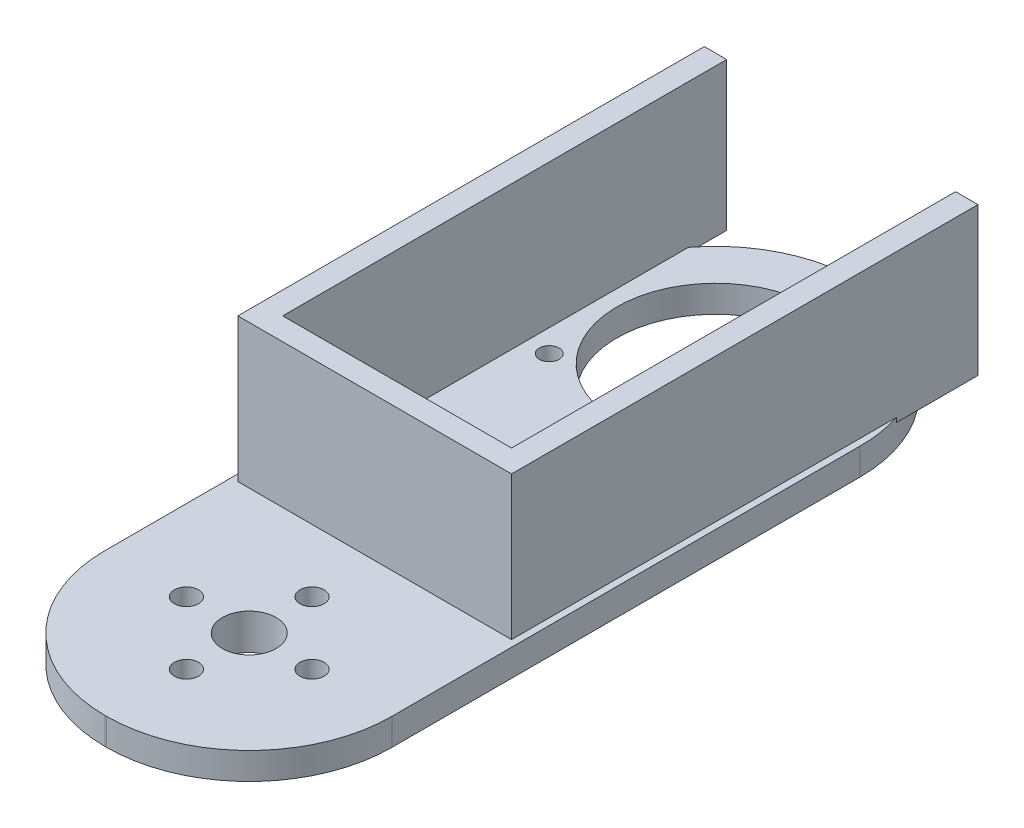
SolidWorks part; units mm, degrees
ref_plane "Front Plane" through (0, 0, 0) normal (0, 0, 1) x (1, 0, 0)
ref_plane "Top Plane" through (0, 0, 0) normal (0, 1, 0) x (1, 0, 0)
ref_plane "Right Plane" through (0, 0, 0) normal (1, 0, 0) x (0, 0, -1)
sketch "S_cyl1" plane through (0, 0, 0) normal (0, 1, 0) x (1, 0, 0)
  circle A0 centre (0, 0) radius 11
  dimension "D1_S_cyl1" = 22
extrude "Boss_1" add sketch "S_cyl1" along normal blind 1.1
ref_plane "PY_p1_000" through (0, 1, 0) normal (0, 1, 0) x (1, 0, 0)
sketch "S_prism2" plane through (0, 1, 0) normal (0, 1, 0) x (1, 0, 0)
  line L0 (-0.1, -16) -> (0.1, -16)
  line L1 (16, -0.1) -> (16, 52.1)
  line L2 (0.1, 68) -> (-0.1, 68)
  line L3 (-16, 52.1) -> (-16, -0.1)
  arc A0 (-16, -0.1) -> (-0.1, -16) centre (-0.1, -0.1) ccw
  arc A1 (0.1, -16) -> (16, -0.1) centre (0.1, -0.1) ccw
  arc A2 (16, 52.1) -> (0.1, 68) centre (0.1, 52.1) ccw
  arc A3 (-0.1, 68) -> (-16, 52.1) centre (-0.1, 52.1) ccw
extrude "Boss_2" add sketch "S_prism2" along normal blind 3
ref_plane "PZ_m66_000" through (0, 0, -66) normal (0, 0, 1) x (1, 0, 0)
sketch "S_box3" plane through (0, 0, -66) normal (0, 0, 1) x (1, 0, 0)
  line L0 (12.76, 3.5) -> (15.26, 3.5)
  line L1 (15.26, 3.5) -> (15.26, 20)
  line L2 (15.26, 20) -> (12.76, 20)
  line L3 (12.76, 20) -> (12.76, 3.5)
  dimension "P1" = 12.76
  dimension "P2" = 3.5
  dimension "P3" = 15.26
  dimension "P4" = 3.5
  dimension "P5" = 15.26
  dimension "P6" = 20
  dimension "P7" = 12.76
  dimension "P8" = 20
extrude "Boss_3" add sketch "S_box3" along normal blind 52.01
sketch "S_box4" plane through (0, 0, -66) normal (0, 0, 1) x (1, 0, 0)
  line L0 (-15.26, 3.5) -> (-12.76, 3.5)
  line L1 (-12.76, 3.5) -> (-12.76, 20)
  line L2 (-12.76, 20) -> (-15.26, 20)
  line L3 (-15.26, 20) -> (-15.26, 3.5)
  dimension "P1" = 15.26
  dimension "P2" = 3.5
  dimension "P3" = 12.76
  dimension "P4" = 3.5
  dimension "P5" = 12.76
  dimension "P6" = 20
  dimension "P7" = 15.26
  dimension "P8" = 20
extrude "Boss_4" add sketch "S_box4" along normal blind 52.01
ref_plane "PZ_m16_490" through (0, 0, -16.49) normal (0, 0, 1) x (1, 0, 0)
sketch "S_box5" plane through (0, 0, -16.49) normal (0, 0, 1) x (1, 0, 0)
  line L0 (-15.26, 3.5) -> (15.26, 3.5)
  line L1 (15.26, 3.5) -> (15.26, 20)
  line L2 (15.26, 20) -> (-15.26, 20)
  line L3 (-15.26, 20) -> (-15.26, 3.5)
  dimension "P1" = 15.26
  dimension "P2" = 3.5
  dimension "P3" = 15.26
  dimension "P4" = 3.5
  dimension "P5" = 15.26
  dimension "P6" = 20
  dimension "P7" = 15.26
  dimension "P8" = 20
extrude "Boss_5" add sketch "S_box5" along normal blind 2.5
ref_plane "PY_m0_100" through (0, -0.1, 0) normal (0, 1, 0) x (1, 0, 0)
sketch "S_hole6" plane through (0, -0.1, 0) normal (0, 1, 0) x (1, 0, 0)
  circle A0 centre (0, 0) radius 3
  dimension "D1_S_hole6" = 6
extrude "Hole_6" cut sketch "S_hole6" along normal blind 4.2
sketch "S_hole7" plane through (0, -0.1, 0) normal (0, 1, 0) x (1, 0, 0)
  circle A0 centre (7, 0) radius 1.35
  dimension "D1_S_hole7" = 2.7
  dimension "P2" = 7
extrude "Hole_7" cut sketch "S_hole7" along normal blind 4.2
sketch "S_hole8" plane through (0, -0.1, 0) normal (0, 1, 0) x (1, 0, 0)
  circle A0 centre (0, -7) radius 1.35
  dimension "D1_S_hole8" = 2.7
  dimension "P2" = 7
extrude "Hole_8" cut sketch "S_hole8" along normal blind 4.2
sketch "S_hole9" plane through (0, -0.1, 0) normal (0, 1, 0) x (1, 0, 0)
  circle A0 centre (-7, 0) radius 1.35
  dimension "D1_S_hole9" = 2.7
  dimension "P2" = 7
extrude "Hole_9" cut sketch "S_hole9" along normal blind 4.2
sketch "S_hole10" plane through (0, -0.1, 0) normal (0, 1, 0) x (1, 0, 0)
  circle A0 centre (0, 7) radius 1.35
  dimension "D1_S_hole10" = 2.7
  dimension "P2" = 7
extrude "Hole_10" cut sketch "S_hole10" along normal blind 4.2
ref_plane "PY_p0_900" through (0, 0.9, 0) normal (0, 1, 0) x (1, 0, 0)
sketch "S_hole11" plane through (0, 0.9, 0) normal (0, 1, 0) x (1, 0, 0)
  circle A0 centre (0, 52) radius 11
  dimension "D1_S_hole11" = 22
  dimension "P2" = 52
extrude "Hole_11" cut sketch "S_hole11" along normal blind 3.2
sketch "S_hole12" plane through (0, 0.9, 0) normal (0, 1, 0) x (1, 0, 0)
  circle A0 centre (-10.25, 43.7) radius 1.1
  dimension "D1_S_hole12" = 2.2
  dimension "P2" = 10.25
  dimension "P3" = 43.7
extrude "Hole_12" cut sketch "S_hole12" along normal blind 3.2
sketch "S_hole13" plane through (0, 0.9, 0) normal (0, 1, 0) x (1, 0, 0)
  circle A0 centre (10.25, 43.7) radius 1.1
  dimension "D1_S_hole13" = 2.2
  dimension "P2" = 10.25
  dimension "P3" = 43.7
extrude "Hole_13" cut sketch "S_hole13" along normal blind 3.2
sketch "S_hole14" plane through (0, 0.9, 0) normal (0, 1, 0) x (1, 0, 0)
  circle A0 centre (-10.25, 19.25) radius 1.1
  dimension "D1_S_hole14" = 2.2
  dimension "P2" = 10.25
  dimension "P3" = 19.25
extrude "Hole_14" cut sketch "S_hole14" along normal blind 3.2
sketch "S_hole15" plane through (0, 0.9, 0) normal (0, 1, 0) x (1, 0, 0)
  circle A0 centre (10.25, 19.25) radius 1.1
  dimension "D1_S_hole15" = 2.2
  dimension "P2" = 10.25
  dimension "P3" = 19.25
extrude "Hole_15" cut sketch "S_hole15" along normal blind 3.2
equation "\"plate_t\" = 3"
equation "\"clearance\" = 0.4"
